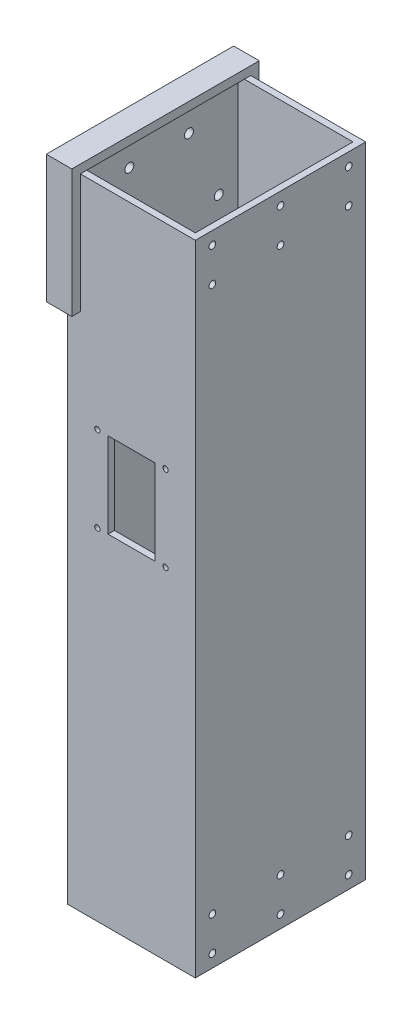
SolidWorks part; units mm, degrees
material "6061-T6 (SS)"
ref_plane "Front Plane" through (0, 0, 0) normal (0, 0, 1) x (1, 0, 0)
ref_plane "Top Plane" through (0, 0, 0) normal (0, 1, 0) x (1, 0, 0)
ref_plane "Right Plane" through (0, 0, 0) normal (1, 0, 0) x (0, 0, -1)
sketch "Sketch1" plane through (0, 0, 0) normal (0, 1, 0) x (1, 0, 0)
  line L0 (3, 3) -> (3, 77)
  line L1 (0, 0) -> (60, 0)
  line L2 (0, 0) -> (0, 80)
  line L3 (0, 80) -> (60, 80)
  line L4 (60, 0) -> (60, 80)
  line L5 (3, 77) -> (57, 77)
  line L6 (57, 3) -> (57, 77)
  line L7 (3, 3) -> (57, 3)
  dimension "D1" = 80
  dimension "D2" = 60
  dimension "D3" = 3
extrude "Boss-Extrude1" add sketch "Sketch1" along normal blind 300
sketch "Sketch2" plane through (0, 0, 0) normal (0, 0, 1) x (1, 0, 0)
  line L0 (30, 300) -> (30, 200) construction
  line L1 (19, 200) -> (41, 200)
  line L2 (19, 200) -> (19, 160)
  line L3 (19, 160) -> (41, 160)
  line L4 (41, 200) -> (41, 160)
  line L5 (0, 300) -> (60, 300) construction
  dimension "D1" = 22
  dimension "D2" = 100
  dimension "D3" = 40
extrude "Cut-Extrude1" cut sketch "Sketch2" against normal up to next
sketch "Sketch3" plane through (0, 0, 0) normal (0, 0, 1) x (1, 0, 0)
  line L0 (19, 200) -> (19, 160) construction
  line L2 (41, 160) -> (41, 200) construction
  line L3 (14, 200) -> (19, 200) construction
  point P0 (14, 200)
  point P11 (46, 200)
  point P12 (46, 160)
  point P13 (14, 160)
  dimension "D1" = 5
  dimension "D5" = 5
  dimension "D6" = 40
  dimension "D3" = 2
  dimension "D4" = 2
hole_wizard "Tap Drill for M3 Tap1" positions "Sketch3" profile "Sketch5" hole size "M3" standard "DIN" end condition up to next
sketch "Sketch5" plane through (14, 200, 0) normal (1, 0, 0) x (0, -1, 0)
  line L0 (0, 0) -> (0, 3)
  line L1 (0, 3) -> (1.25, 3)
  line L2 (1.25, 3) -> (1.25, 0)
  line L5 (1.25, 0) -> (0, 0)
  line L11 (0, -6.35) -> (0, 107.95) construction
  dimension "Thru Hole Dia." = 2.5
  dimension "Thru Hole Depth" = 3
sketch "Sketch8" plane through (0, 0, 0) normal (-1, 0, 0) x (0, 0, 1)
  point P0 (-8, 6)
  point P8 (-40, 6)
  point P9 (-72, 6)
  point P10 (-40, 22)
  point P11 (-72, 22)
  point P12 (-8, 22)
  dimension "D1" = 3
  dimension "D2" = 2
hole_wizard "Tap Drill for M3 Helicoil1" positions "Sketch8" profile "Sketch7" hole size "M3x0.5" standard "DIN" end condition through all
sketch "Sketch7" plane through (0, 6, -8) normal (0, 1, 0) x (0, 0, 1)
  line L0 (0, 0) -> (0, 60)
  line L1 (0, 60) -> (1.575, 60)
  line L2 (1.575, 60) -> (1.575, 0)
  line L5 (1.575, 0) -> (0, 0)
  line L11 (0, -6.35) -> (0, 107.95) construction
  dimension "Thru Hole Dia." = 3.15
  dimension "Thru Hole Depth" = 60
sketch "Sketch11" plane through (60, 0, 0) normal (1, 0, 0) x (0, 0, -1)
  line L3 (40, 300) -> (40, 248.3318) construction
  line L4 (0, 300) -> (80, 300) construction
  point P45 (8, 294)
  point P50 (40, 294)
  point P51 (72, 294)
  point P52 (40, 278)
  point P53 (72, 278)
  point P54 (8, 278)
  dimension "D1" = 3
  dimension "D3" = 6
  dimension "D2" = 2
hole_wizard "Tap Drill for M3 Helicoil2" positions "Sketch11" profile "Sketch10" hole size "M3x0.5" standard "DIN" end condition up to next
sketch "Sketch10" plane through (60, 294, -8) normal (0, 1, 0) x (0, 0, -1)
  line L0 (0, 0) -> (0, 3)
  line L1 (0, 3) -> (1.575, 3)
  line L2 (1.575, 3) -> (1.575, 0)
  line L5 (1.575, 0) -> (0, 0)
  line L11 (0, -6.35) -> (0, 107.95) construction
  dimension "Thru Hole Dia." = 3.15
  dimension "Thru Hole Depth" = 3
sketch "Sketch14" plane through (0, 0, 0) normal (-1, 0, 0) x (0, 0, 1)
  point P0 (-68, 256)
  point P3 (-12, 256)
  point P6 (-26, 288)
  point P9 (-54, 288)
hole_wizard "Tap Drill for M5 Tap1" positions "Sketch14" profile "Sketch13" hole size "M5" standard "DIN" end condition up to next
sketch "Sketch13" plane through (0, 256, -68) normal (0, 1, 0) x (0, 0, 1)
  line L0 (0, 0) -> (0, 3)
  line L1 (0, 3) -> (2.1, 3)
  line L2 (2.1, 3) -> (2.1, 0)
  line L5 (2.1, 0) -> (0, 0)
  line L11 (0, -6.35) -> (0, 107.95) construction
  dimension "Thru Hole Dia." = 4.2
  dimension "Thru Hole Depth" = 3
sketch "Sketch15" plane through (0, 0, 0) normal (-1, 0, 0) x (0, 0, 1)
  line L0 (-80, 244) -> (-84, 244)
  line L1 (-80, 300) -> (-80, 0) construction
  line L2 (-84, 244) -> (-84, 304)
  line L3 (-84, 304) -> (4, 304)
  line L4 (4, 304) -> (4, 244)
  line L5 (4, 244) -> (0, 244)
  line L6 (0, 300) -> (0, 0) construction
  line L7 (0, 244) -> (0, 300)
  line L8 (0, 300) -> (-80, 300)
  line L9 (-80, 300) -> (0, 300) construction
  line L10 (-80, 300) -> (-80, 244)
  dimension "D1" = 4
  dimension "D2" = 4
  dimension "D3" = 60
extrude "Boss-Extrude2" add sketch "Sketch15" against normal blind 6 separate body
sketch "Sketch16" plane through (0, 0, 0) normal (-1, 0, 0) x (0, 0, 1)
  line L0 (-40, 304) -> (-40, 296) construction
  line L1 (-84, 304) -> (4, 304)
  line L2 (-84, 304) -> (-84, 244)
  line L3 (-84, 244) -> (4, 244)
  line L4 (4, 304) -> (4, 244)
  line L5 (-77.5, 282) -> (-2.5, 282)
  line L6 (-77.5, 282) -> (-77.5, 262)
  line L7 (-77.5, 262) -> (-2.5, 262)
  line L8 (-2.5, 282) -> (-2.5, 262)
  line L9 (-47.5, 282) -> (-32.5, 282)
  line L10 (-47.5, 282) -> (-47.5, 296)
  line L11 (-47.5, 296) -> (-32.5, 296)
  line L12 (-32.5, 282) -> (-32.5, 296)
  line L13 (-40, 296) -> (-40, 262) construction
  line L14 (-40, 262) -> (-40, 252) construction
  line L15 (-60, 262) -> (-20, 262)
  line L16 (-60, 262) -> (-60, 252)
  line L17 (-60, 252) -> (-20, 252)
  line L18 (-20, 262) -> (-20, 252)
  circle A0 centre (-54, 288) radius 2.9
  circle A1 centre (-26, 288) radius 2.9
  circle A2 centre (-12, 256) radius 2.9
  circle A3 centre (-68, 256) radius 2.9
  point P18 (-40, 304)
  line M22 (-80, 244) -> (-80, 300)
  line M23 (-80, 300) -> (0, 300)
  line M24 (0, 300) -> (0, 244)
  line M25 (0, 244) -> (4, 244)
  line M26 (4, 244) -> (4, 304)
  line M27 (4, 304) -> (-84, 304)
  line M28 (-84, 304) -> (-84, 244)
  line M29 (-84, 244) -> (-80, 244)
  dimension "D6" = 5.8
  dimension "D7" = 40
  dimension "D1" = 75
  dimension "D2" = 15
  dimension "D3" = 20
  dimension "D4" = 8
  dimension "D5" = 14
  dimension "D8" = 10
extrude "Boss-Extrude3" add sketch "Sketch16" along normal blind 6 contours M29 M22 M23 M24 M25 M26 M27 M28 | L3 A3 A2 A1 A0 L7 L18 L17 L16 L6 L5 L10 L11 L12 L8 M22 M24 M23 region at (0, 302.9349, -40) region at (0, 272, -79.0235)
fillet "Fillet1" radius 2 12 edges at (-3, 262, -2.5) (-3, 282, -2.5) (-3, 282, -32.5) (-3, 296, -47.5) (-3, 282, -47.5) (-3, 282, -77.5) (-3, 262, -77.5) (-3, 262, -60) (-3, 252, -60) (-3, 252, -20) (-3, 262, -20) (-3, 296, -32.5)
